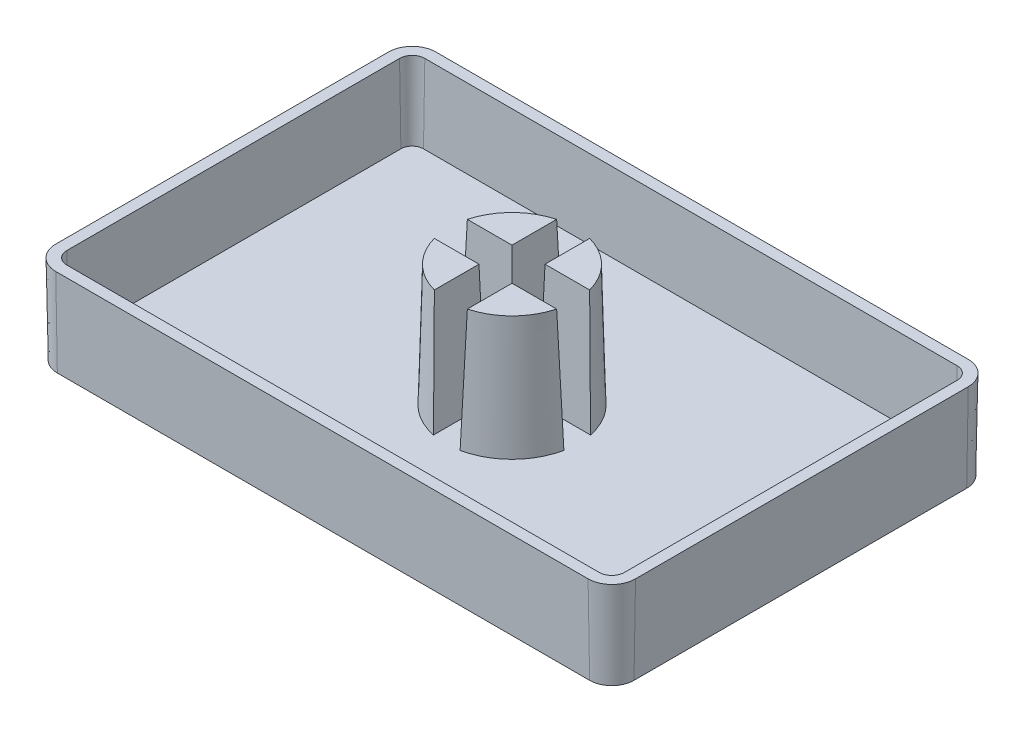
SolidWorks part; units mm, degrees
ref_plane "Front Plane" through (0, 0, 0) normal (0, 0, 1) x (1, 0, 0)
ref_plane "Top Plane" through (0, 0, 0) normal (0, 1, 0) x (1, 0, 0)
ref_plane "Right Plane" through (0, 0, 0) normal (1, 0, 0) x (0, 0, -1)
sketch "Sketch1" plane through (0, 0, 0) normal (0, 1, 0) x (1, 0, 0)
  line L1 (-12, -8.5) -> (12, -8.5)
  line L2 (-13, -7.5) -> (-13, 7.5)
  line L3 (-12, 8.5) -> (12, 8.5)
  line L4 (13, -7.5) -> (13, 7.5)
  line L5 (-13, -8.5) -> (13, 8.5) construction
  line L6 (-13, 8.5) -> (13, -8.5) construction
  arc A0 (-13, 7.5) -> (-12, 8.5) centre (-12, 7.5) cw
  arc A1 (13, 7.5) -> (12, 8.5) centre (12, 7.5) ccw
  arc A2 (13, -7.5) -> (12, -8.5) centre (12, -7.5) cw
  arc A3 (-12, -8.5) -> (-13, -7.5) centre (-12, -7.5) cw
  point P0 (0, 0)
  dimension "D3" = 1
  dimension "D1" = 26
  dimension "D2" = 17
extrude "Boss-Extrude1" add sketch "Sketch1" along normal blind 4 draft 1 draft outward yes
shell "Shell1" thickness 0.5 removed face at (0, 4, 0)
sketch "Sketch2" plane through (0, 0.5, 0) normal (0, 1, 0) x (1, 0, 0)
  line L0 (-0.6, -2.9394) -> (-0.6, -0.6)
  line L1 (2.9394, 0.6) -> (0.6, 0.6)
  line L2 (0, -2.2) -> (0, 2.2) construction
  line L3 (-2.2, 0) -> (2.2, 0) construction
  line L4 (2.9394, -0.6) -> (0.6, -0.6)
  line L5 (0.6, -2.9394) -> (0.6, -0.6)
  line L6 (-0.6, 0.6) -> (-0.6, 2.9394)
  line L7 (0.6, 0.6) -> (0.6, 2.9394)
  line L8 (-0.6, -0.6) -> (-2.9394, -0.6)
  line L9 (-0.6, 0.6) -> (-2.9394, 0.6)
  arc A0 (-2.9394, -0.6) -> (-0.6, -2.9394) centre (0, 0) ccw
  arc A1 (2.9394, 0.6) -> (0.6, 2.9394) centre (0, 0) ccw
  arc A2 (0.6, -2.9394) -> (2.9394, -0.6) centre (0, 0) ccw
  arc A3 (-0.6, 2.9394) -> (-2.9394, 0.6) centre (0, 0) ccw
  point P18 (0, 0)
  dimension "D1" = 0.6
  dimension "D2" = 0.6
extrude "Boss-Extrude2" add sketch "Sketch2" along normal blind 5.5 draft 1.5
